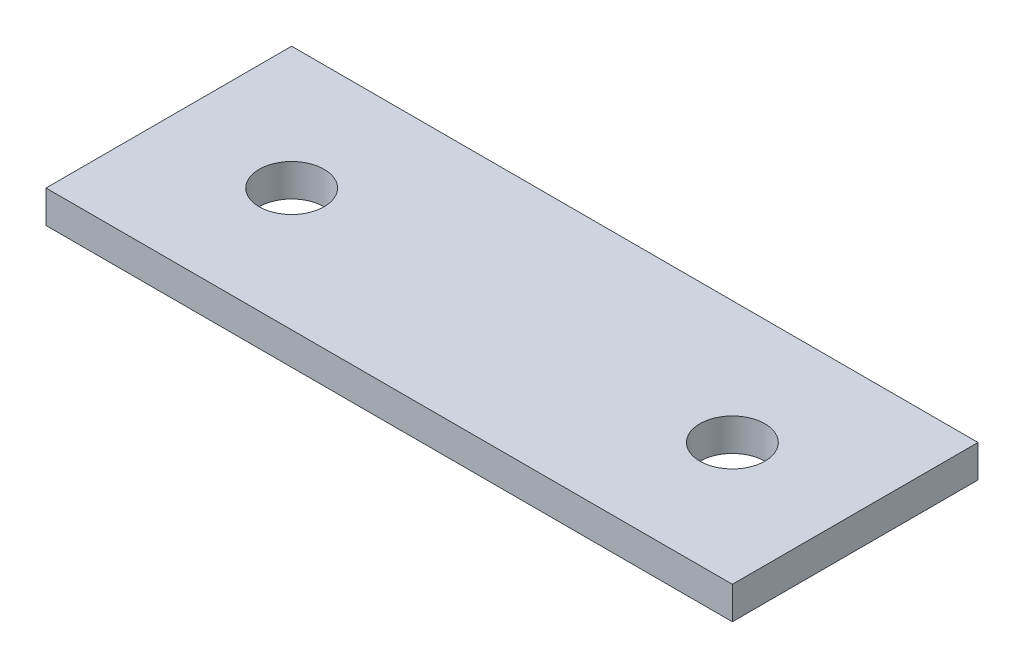
SolidWorks part; units mm, degrees
ref_plane "Front Plane" through (0, 0, 0) normal (0, 0, 1) x (1, 0, 0)
ref_plane "Top Plane" through (0, 0, 0) normal (0, 1, 0) x (1, 0, 0)
ref_plane "Right Plane" through (0, 0, 0) normal (1, 0, 0) x (0, 0, -1)
sketch "Sketch1" plane through (0, 0, 0) normal (0, 1, 0) x (1, 0, 0)
  line L0 (-10.765, 0) -> (10.765, 0) construction
  line L1 (16.765, -6) -> (-16.765, -6)
  line L2 (16.765, -6) -> (16.765, 6)
  line L3 (16.765, 6) -> (-16.765, 6)
  line L4 (-16.765, -6) -> (-16.765, 6)
  line L5 (16.765, -6) -> (-16.765, 6) construction
  line L6 (16.765, 6) -> (-16.765, -6) construction
  circle A0 centre (-10.765, 0) radius 1.5875
  circle A1 centre (10.765, 0) radius 1.5875
  circle A2 centre (-10.765, 0) radius 5 construction
  point P0 (0, 0)
  point P8 (0, 0)
  dimension "D1" = 3.175
  dimension "D4" = 10
  dimension "D2" = 21.53
  dimension "D3" = 12
  dimension "D5" = 6
extrude "Boss-Extrude1" add sketch "Sketch1" along normal mid plane 1.5875
